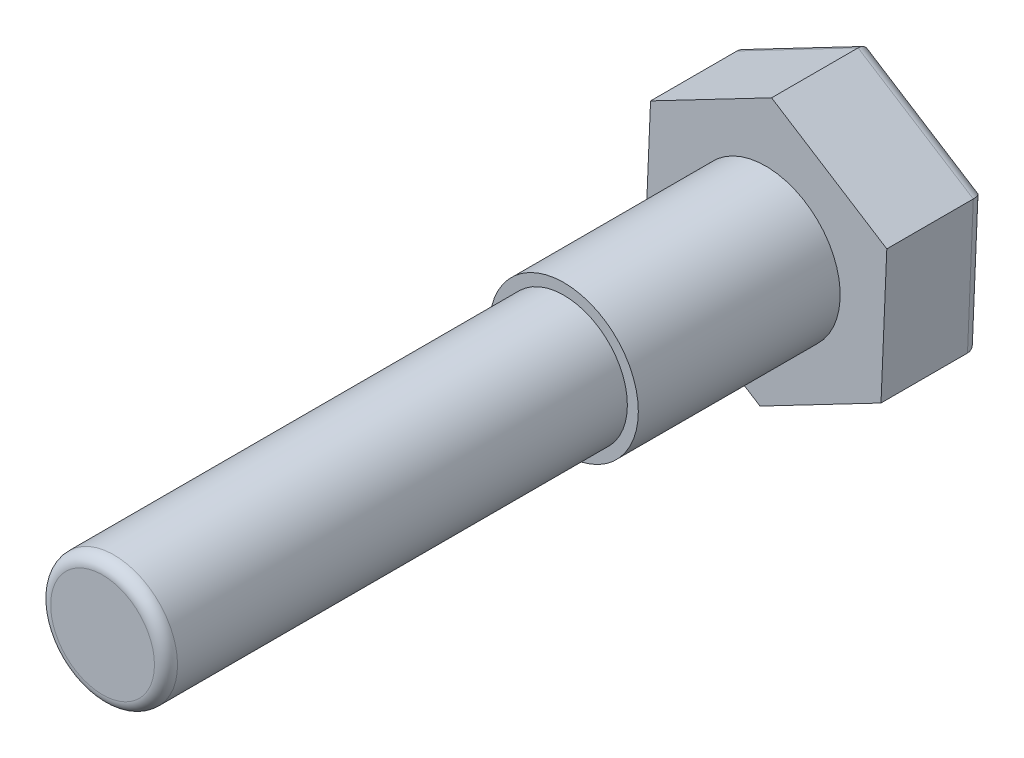
SolidWorks part; units mm, degrees
ref_plane "前视" through (0, 0, 0) normal (0, 0, 1) x (1, 0, 0)
ref_plane "上视" through (0, 0, 0) normal (0, 1, 0) x (1, 0, 0)
ref_plane "右视" through (0, 0, 0) normal (1, 0, 0) x (0, 0, -1)
sketch "草图1" plane through (0, 0, 0) normal (0, 0, 1) x (1, 0, 0)
  line L1 (20.9842, 10.9543) -> (1.0054, 23.65)
  line L2 (1.0054, 23.65) -> (-19.9788, 12.6957)
  line L3 (-19.9788, 12.6957) -> (-20.9842, -10.9543)
  line L4 (-20.9842, -10.9543) -> (-1.0054, -23.65)
  line L5 (-1.0054, -23.65) -> (19.9788, -12.6957)
  line L6 (19.9788, -12.6957) -> (20.9842, 10.9543)
  circle A0 centre (0, 0) radius 20.5 construction
  dimension "D1" = 47.3
  dimension "D2" = 41
extrude "基体-拉伸" add sketch "草图1" along normal blind 17
sketch "草图2" plane through (0, 0, 17) normal (0, 0, 1) x (1, 0, 0)
  circle A0 centre (0, 0) radius 12.9
  dimension "D1" = 25.8
extrude "凸台-拉伸1" add sketch "草图2" along normal blind 35
fillet "圆角3" radius 2 6 edges at (10.9948, 17.3021, 0) (-9.4867, 18.1729, 0) (-20.4815, 0.8707, 0) (-10.9948, -17.3021, 0) (9.4867, -18.1729, 0) (20.4815, -0.8707, 0)
sketch "草图3" plane through (0, 0, 52) normal (0, 0, 1) x (1, 0, 0)
  circle A0 centre (0, 0) radius 11
  dimension "D1" = 22
extrude "凸台-拉伸2" add sketch "草图3" along normal blind 80
fillet "圆角4" radius 2 1 edges at (11, 0, 132)
